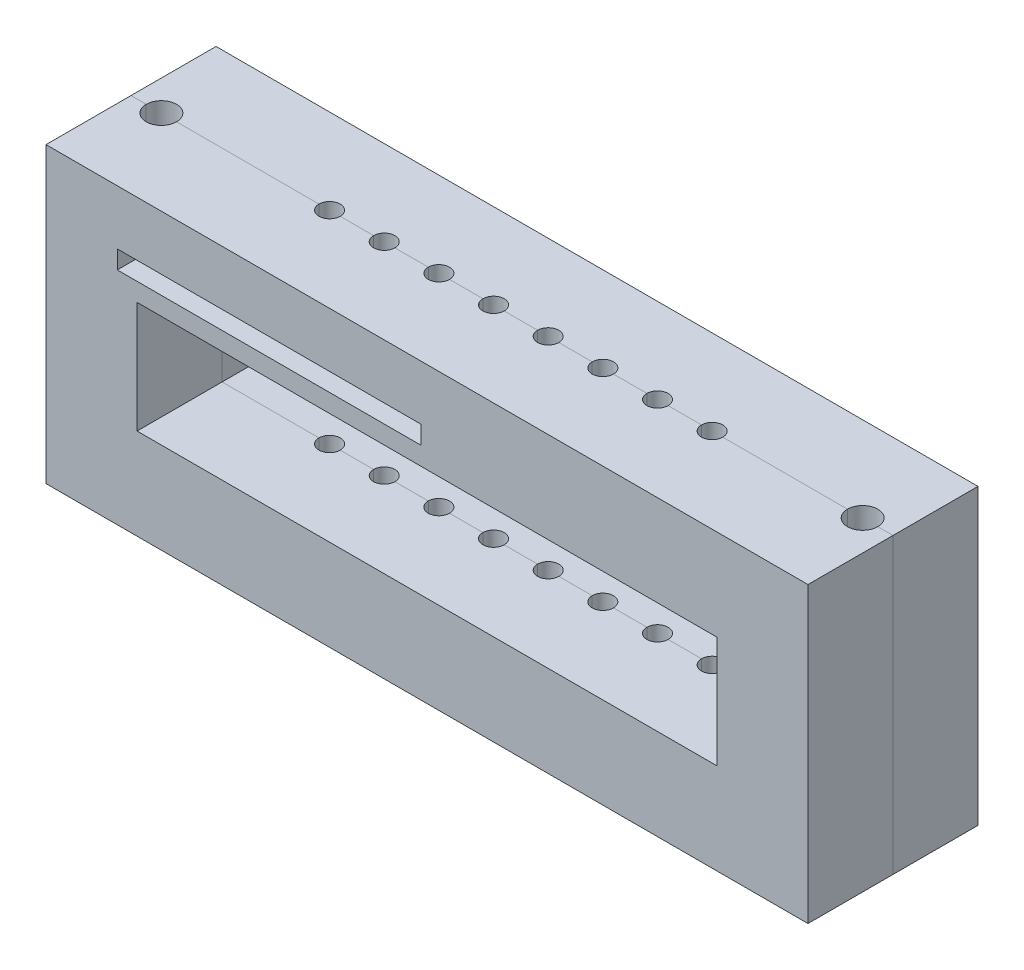
SolidWorks part; units mm, degrees
ref_plane "Front Plane" through (0, 0, 0) normal (0, 0, 1) x (1, 0, 0)
ref_plane "Top Plane" through (0, 0, 0) normal (0, 1, 0) x (1, 0, 0)
ref_plane "Right Plane" through (0, 0, 0) normal (1, 0, 0) x (0, 0, -1)
sketch "Base sketch" plane through (0, 0, 0) normal (0, 0, 1) x (1, 0, 0)
  line L1 (47.74, -9.175) -> (-47.74, -9.175)
  line L2 (47.74, -9.175) -> (47.74, 9.175)
  line L3 (47.74, 9.175) -> (-47.74, 9.175)
  line L4 (-47.74, -9.175) -> (-47.74, 9.175)
  line L5 (47.74, -9.175) -> (-47.74, 9.175) construction
  line L6 (47.74, 9.175) -> (-47.74, -9.175) construction
  line L7 (62.74, -24.175) -> (-62.74, -24.175)
  line L8 (62.74, -24.175) -> (62.74, 24.175)
  line L9 (62.74, 24.175) -> (-62.74, 24.175)
  line L10 (-62.74, -24.175) -> (-62.74, 24.175)
  line L11 (62.74, -24.175) -> (-62.74, 24.175) construction
  line L12 (62.74, 24.175) -> (-62.74, -24.175) construction
  point P0 (0, 0)
  point P6 (0, 0)
  dimension "D1" = 95.48
  dimension "D2" = 18.35
  dimension "D3" = 15
  dimension "D4" = 15
extrude "Base extrusion" add sketch "Base sketch" along normal mid plane 28
ref_axis "Z-axis" through (0, 26.5925, 0) along (0, -1, 0)
ref_plane "Origin reflection plane" through (0, 0, 0) normal (-0.7071, 0, 0.7071) x (0, -1, 0)
sketch "LED hole sketch" plane through (0, -9.175, 0) normal (0, 1, 0) x (1, 0, 0)
  line L0 (-16.5997, 0) -> (17.6886, 0) construction
  line L1 (-47.74, 0) -> (47.74, 0) construction
  line L4 (47.74, 14) -> (-47.74, 14)
  line L5 (-47.74, 14) -> (-47.74, -14)
  line L6 (-47.74, -14) -> (47.74, -14)
  line L7 (47.74, -14) -> (47.74, 14)
  line L8 (47.74, 14) -> (-47.74, 14) construction
  line L9 (-47.74, 14) -> (-47.74, -14) construction
  line L10 (-47.74, -14) -> (47.74, -14) construction
  line L11 (47.74, -14) -> (47.74, 14) construction
  circle A0 centre (-30.04, 0) radius 3.5
  dimension "D3" = 7
  dimension "D2" = 17.7
extrude "LED hole" cut sketch "LED hole sketch" against normal up to surface (15 mm away) from offset 3 contours A0 up to face at (0, -24.175, 0) offset against normal yes
sketch "lens hole sketch" plane through (0, -12.175, 0) normal (0, -1, 0) x (1, 0, 0)
  circle A0 centre (-30.04, 0) radius 3.5 construction
  circle A1 centre (-30.04, 0) radius 3.5 construction
  circle A2 centre (-30.04, 0) radius 1.75
  dimension "D1" = 3.5
extrude "lens hole" cut sketch "lens hole sketch" against normal up to surface (3 mm away) up to face at (0, -9.175, 0)
pattern_linear "bottom linear pattern" count 8 spacing 9 along (1, 0, 0) of "LED hole", "lens hole"
sketch "filter slot sketch" plane through (0, 0, 14) normal (0, 0, 1) x (1, 0, 0)
  line L0 (47.74, 9.175) -> (-47.74, 9.175) construction
  line L1 (-51, 15.175) -> (-1, 15.175)
  line L2 (-51, 15.175) -> (-51, 12.175)
  line L3 (-51, 12.175) -> (-1, 12.175)
  line L4 (-1, 15.175) -> (-1, 12.175)
  dimension "D2" = 50
  dimension "D3" = 3
extrude "filter slot cut" cut sketch "filter slot sketch" against normal blind 20
sketch "Sketch6" plane through (0, 9.175, 0) normal (0, -1, 0) x (1, 0, 0)
  line L1 (-31.79, 1.75) -> (-28.29, 1.75) construction
  line L2 (-31.79, 1.75) -> (-31.79, -1.75) construction
  line L3 (-31.79, -1.75) -> (-28.29, -1.75) construction
  line L4 (-28.29, 1.75) -> (-28.29, -1.75) construction
  line L5 (-31.79, 1.75) -> (-28.29, -1.75) construction
  line L6 (-31.79, -1.75) -> (-28.29, 1.75) construction
  circle A0 centre (-30.04, 0) radius 1.75 construction
  circle A1 centre (-30.04, 0) radius 1.75
extrude "photodiode hole" cut sketch "Sketch6" against normal up to surface (15 mm away) up to face at (0, 24.175, 0)
sketch "Sketch9" plane through (0, 9.175, 0) normal (0, -1, 0) x (1, 0, 0)
  circle A0 centre (-30.04, 0) radius 3.5 construction
  circle A1 centre (-30.04, 0) radius 1.75 construction
  circle A2 centre (-30.04, 0) radius 3.5
  circle A3 centre (-30.04, 0) radius 1.75
extrude "Light shade" add sketch "Sketch9" along normal blind 5
pattern_linear "photodiode linear pattern" count 8 spacing 9 along (1, 0, 0) of "Light shade", "photodiode hole"
pattern_circular "photodiode and filter circular pattern" count 2 every 180 about axis through (0, 26.5925, 0) along (0, -1, 0) of "filter slot cut"
sketch "bolt hole sketch" plane through (0, 24.175, 0) normal (0, 1, 0) x (1, 0, 0)
  line L0 (-62.74, -14) -> (-62.74, 14) construction
  line L2 (-26.4561, 0) -> (23.5832, 0) construction
  line L3 (0, -15.4) -> (0, 15.4) construction
  circle A0 centre (-57.74, 0) radius 2.5
  circle A1 centre (57.74, 0) radius 2.5
  dimension "D2" = 5
  dimension "D1" = 5
extrude "Bolt hole" cut sketch "bolt hole sketch" against normal up to surface (48.35 mm away) up to face at (-21.04, -24.175, 3.5)
split "Split1" trim tools "Front Plane" bodies to split 110 resulting bodies 117 118
equation "\"D1@Base sketch\" = 85.48 + 10"
equation "\"D2@Base sketch\" = 14.35 + 4"
equation "\"D1@Base extrusion\" = 2 * 9 + 5 + 5"
equation "\"D2@LED hole sketch\" = 12.7 + 5"
equation "\"D3@LED hole sketch\" = 7"
equation "\"D2@filter slot sketch\" = 50"
